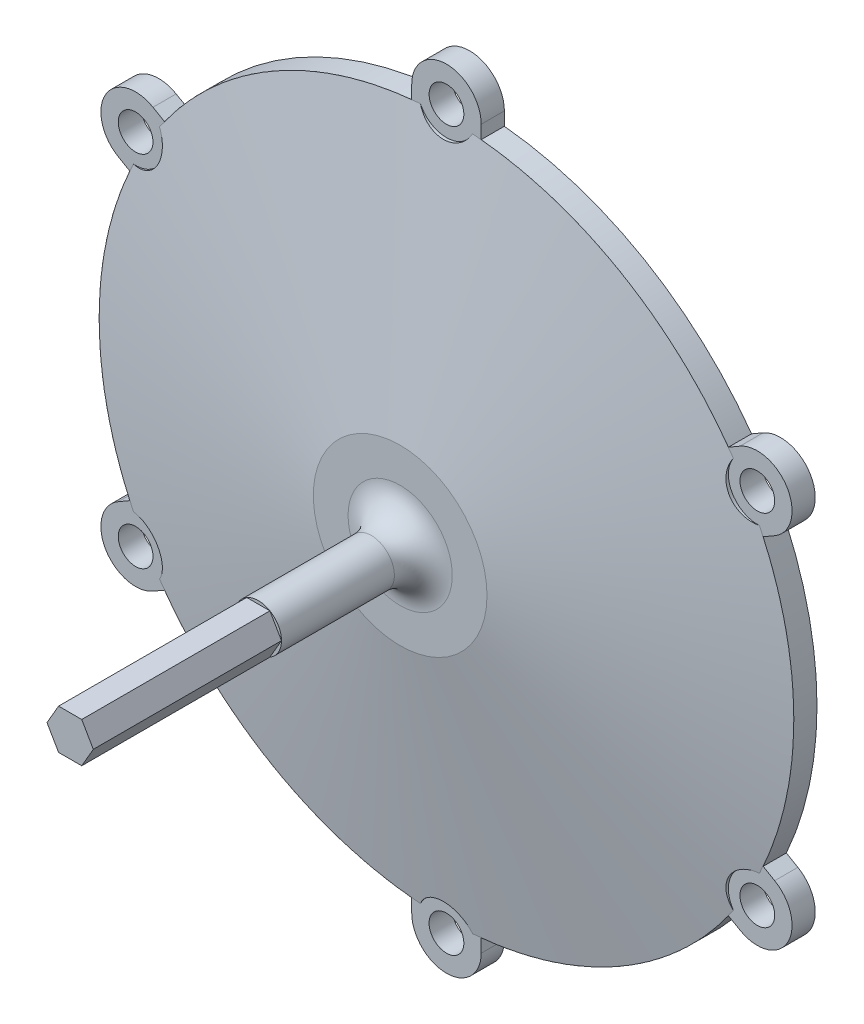
SolidWorks part; units mm, degrees
other "Markup1"
sketch "Sketch15" plane through (-60, 68, 48) normal (-0.9801, 0.1341, 0.1467) x (0.1373, -0.0767, 0.9876)
material "PETG"
ref_plane "Front Plane" through (0, 0, 0) normal (0, 0, 1) x (1, 0, 0)
ref_plane "Top Plane" through (0, 0, 0) normal (0, 1, 0) x (1, 0, 0)
ref_plane "Right Plane" through (0, 0, 0) normal (1, 0, 0) x (0, 0, -1)
sketch "Sketch1" plane through (0, 0, 0) normal (0, 0, 1) x (1, 0, 0)
  line L0 (-6, 62) -> (-6, 59.6992)
  line L1 (6, 62) -> (6, 59.6992)
  line L2 (50.6936, 36.1962) -> (48.7011, 35.0458)
  line L3 (56.6936, 25.8038) -> (54.7011, 24.6535)
  line L4 (56.6936, -25.8038) -> (54.7011, -24.6535)
  line L5 (50.6936, -36.1962) -> (48.7011, -35.0458)
  line L6 (6, -62) -> (6, -59.6992)
  line L7 (-6, -62) -> (-6, -59.6992)
  line L8 (-50.6936, -36.1962) -> (-48.7011, -35.0458)
  line L9 (-56.6936, -25.8038) -> (-54.7011, -24.6535)
  line L10 (-56.6936, 25.8038) -> (-54.7011, 24.6535)
  line L11 (-50.6936, 36.1962) -> (-48.7011, 35.0458)
  line L12 (0, 0) -> (6, 59.6992) construction
  circle A0 centre (0, 0) radius 57
  circle A1 centre (0, 0) radius 60
  arc A2 (6, 62) -> (-6, 62) centre (0, 62) ccw
  arc A3 (56.6936, 25.8038) -> (50.6936, 36.1962) centre (53.6936, 31) ccw
  arc A4 (50.6936, -36.1962) -> (56.6936, -25.8038) centre (53.6936, -31) ccw
  arc A5 (-6, -62) -> (6, -62) centre (0, -62) ccw
  arc A6 (-56.6936, -25.8038) -> (-50.6936, -36.1962) centre (-53.6936, -31) ccw
  arc A7 (-50.6936, 36.1962) -> (-56.6936, 25.8038) centre (-53.6936, 31) ccw
  dimension "D1" = 120
  dimension "D2" = 3
  dimension "D3" = 6
  dimension "D4" = 62
  dimension "D5" = 6
extrude "Boss-Extrude1" add sketch "Sketch1" along normal blind 4 contours L11 A7 L10 A1 | L1 A2 L0 A1 | L3 A3 L2 A1 | L5 A4 L4 A1 | L7 A5 L6 A1 | L9 A6 L8 A1 | A0 A1 region at (0, 63.4372, 0) region at (0, 58.3029, 0) region at (-54.9382, 31.7186, 0) region at (54.9382, 31.7186, 0) region at (-54.9382, -31.7186, 0) region at (54.9382, -31.7186, 0) region at (0, -63.4372, 0)
sketch "Sketch3" plane through (0, 0, 0) normal (0, 1, 0) x (1, 0, 0)
  line L0 (0, -4) -> (60, -4)
  line L1 (-6, -4) -> (6, -4) construction
  line L2 (60, -4) -> (15, -12)
  line L3 (15, -12) -> (0, -12)
  line L4 (0, -12) -> (0, -4)
  line L5 (48.7011, 0) -> (6, 0) construction
  line L6 (48.7011, 0) -> (6, 0) construction
  line L7 (0, -4) -> (60, -4)
  line L8 (0, -4) -> (0, -0.5)
  line L9 (0, -0.5) -> (57, -0.5)
  line L13 (57, -0.5) -> (57, -4)
  line L15 (-57, -4) -> (57, -4) construction
  dimension "D1" = 12
  dimension "D2" = 15
  dimension "D3" = 0.5
  dimension "D4" = 3
revolve "Revolve1" add sketch "Sketch3" angle 360 about L4 region at (28.5, 0, 2.25) region at (21, 0, 7.2)
sketch "Sketch4" plane through (0, 0, 0.5) normal (0, 0, 1) x (1, 0, 0)
  circle A0 centre (0, 0) radius 14
  dimension "D1" = 28
extrude "Cut-Extrude1" cut sketch "Sketch4" along normal blind 7 contours A0
sketch "Sketch9" plane through (0, 0, 7.5) normal (0, 0, -1) x (-1, 0, 0)
  circle A0 centre (0, 0) radius 11.5
  dimension "D1" = 23
extrude "Cut-Extrude4" cut sketch "Sketch9" against normal blind 0.5
sketch "Sketch10" plane through (0, 0, 12) normal (0, 0, 1) x (1, 0, 0)
  circle A0 centre (0, 0) radius 4
  dimension "D1" = 8
extrude "Boss-Extrude2" add sketch "Sketch10" along normal blind 57
fillet "Fillet1" radius 5 1 edges at (4, 0, 12)
sketch "Sketch7" plane through (0, 0, 4) normal (0, 0, 1) x (1, 0, 0)
  circle A0 centre (0, 62) radius 3
  arc A1 (6, 62) -> (-6, 62) centre (0, 62) ccw construction
  dimension "D1" = 6
extrude "Cut-Extrude2" cut sketch "Sketch7" against normal through all
sketch "Sketch8" plane through (0, 0, 4) normal (0, 0, 1) x (1, 0, 0)
  circle A0 centre (0, 62) radius 5
  dimension "D1" = 10
extrude "Cut-Extrude3" cut sketch "Sketch8" along normal through all
pattern_circular "CirPattern6" count 6 over 360 about axis through (0, 0, 4) along (0, 0, 1) of "Cut-Extrude2", "Cut-Extrude3"
sketch "Sketch11" plane through (0, 0, 69) normal (0, 0, 1) x (1, 0, 0)
  line L5 (2, 3.4641) -> (-2, 3.4641)
  line L6 (-2, 3.4641) -> (-4, 0)
  line L7 (-4, 0) -> (-2, -3.4641)
  line L8 (-2, -3.4641) -> (2, -3.4641)
  line L9 (2, -3.4641) -> (4, 0)
  line L10 (4, 0) -> (2, 3.4641)
  circle A1 centre (0, 0) radius 3.4641 construction
  circle A2 centre (0, 0) radius 4 construction
  circle A3 centre (0, 0) radius 4
  circle M5 centre (0, 0) radius 4
extrude "Cut-Extrude5" cut sketch "Sketch11" against normal blind 32.5 contours L6 M5 | L5 M5 | L10 M5 | L9 M5 | L8 M5 | L7 M5 region at (3.1867, 1.8399, 69) region at (0, 3.6797, 69) region at (-3.1867, 1.8399, 69) region at (3.1867, -1.8399, 69) region at (-3.1867, -1.8399, 69) region at (0, -3.6797, 69)
